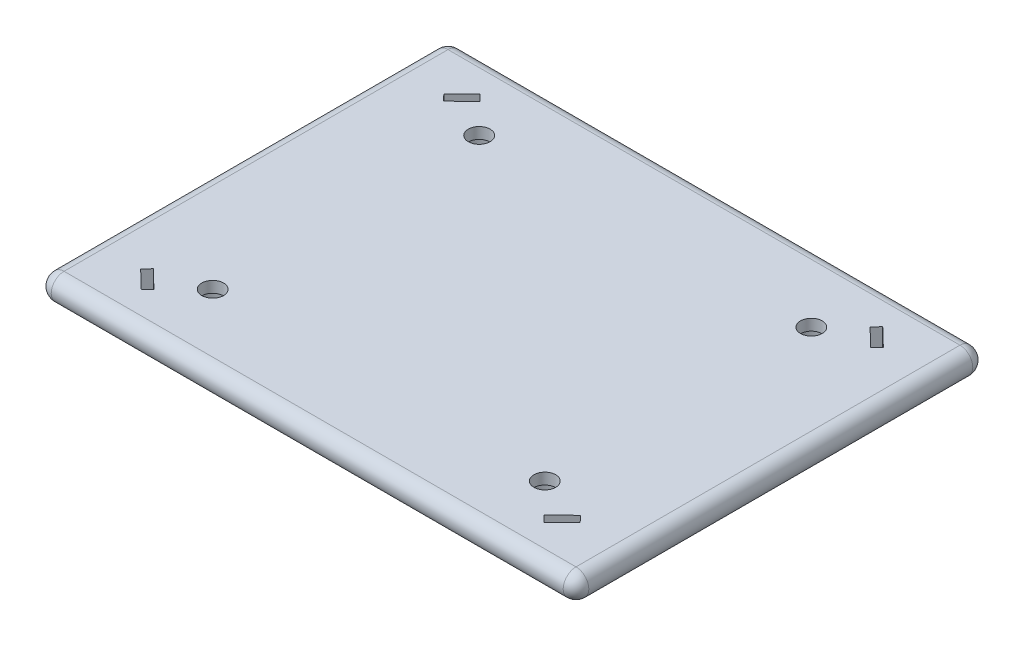
SolidWorks part; units mm, degrees
ref_plane "前视基准面" through (0, 0, 0) normal (0, 0, 1) x (1, 0, 0)
ref_plane "上视基准面" through (0, 0, 0) normal (0, 1, 0) x (1, 0, 0)
ref_plane "右视基准面" through (0, 0, 0) normal (1, 0, 0) x (0, 0, -1)
other "碳"
sketch "草图2" plane through (0, 0, 0) normal (0, 1, 0) x (1, 0, 0)
  line L0 (0, 0) -> (-72.7924, 0) construction
  line L5 (0, 151.7592) -> (0, 201.8849) construction
  line L6 (-200, 160) -> (200, 160)
  line L7 (210, 150) -> (210, 0)
  line L8 (210, 0) -> (210, -150)
  line L9 (200, -160) -> (-200, -160)
  line L10 (-210, 0) -> (-210, -150)
  line L11 (-210, 150) -> (-210, 0)
  line L12 (-157.3287, 132.3214) -> (-171.7157, 118.4284)
  line L13 (-157.3287, 132.3214) -> (-152.4662, 127.2859)
  line L14 (-171.7157, 118.4284) -> (-166.8532, 113.393)
  line L15 (-152.4662, 127.2859) -> (-166.8532, 113.393)
  line L16 (-171.7157, -118.4284) -> (-166.8532, -113.393)
  line L17 (-152.4662, -127.2859) -> (-166.8532, -113.393)
  line L18 (-157.3287, -132.3214) -> (-152.4662, -127.2859)
  line L19 (-157.3287, -132.3214) -> (-171.7157, -118.4284)
  line L20 (157.3287, -132.3214) -> (171.7157, -118.4284)
  line L21 (157.3287, -132.3214) -> (152.4662, -127.2859)
  line L22 (152.4662, -127.2859) -> (166.8532, -113.393)
  line L23 (171.7157, -118.4284) -> (166.8532, -113.393)
  line L24 (171.7157, 118.4284) -> (166.8532, 113.393)
  line L25 (152.4662, 127.2859) -> (166.8532, 113.393)
  line L26 (157.3287, 132.3214) -> (152.4662, 127.2859)
  line L27 (157.3287, 132.3214) -> (171.7157, 118.4284)
  arc A0 (210, -150) -> (200, -160) centre (200, -150) cw
  arc A1 (-210, -150) -> (-200, -160) centre (-200, -150) ccw
  arc A2 (200, 160) -> (210, 150) centre (200, 150) cw
  arc A3 (-210, 150) -> (-200, 160) centre (-200, 150) cw
  circle A4 centre (-129.7453, 104.1081) radius 9.7639 construction
  circle A5 centre (-129.7453, -104.1081) radius 9.7639 construction
  circle A6 centre (129.7453, -104.1081) radius 9.7639 construction
  circle A7 centre (129.7453, 104.1081) radius 9.7639 construction
  point P12 (0, 160)
  point P13 (0, -160)
  point P16 (210, -160)
  point P19 (-210, -160)
  point P22 (210, 160)
  point P25 (-210, 160)
  dimension "D1" = 10
  dimension "D2" = 150
  dimension "D3" = 400
  dimension "D4" = 20
  dimension "D5" = 7
extrude "凸台-拉伸1" add sketch "草图2" along normal blind 20
hole_wizard "5/8 六角头螺钉的柱形沉头孔1" positions "草图15" profile "草图16" counterbore size "5/8" standard "ANSI Inch" end condition through all
sketch "草图15" plane through (0, 0, 0) normal (0, -1, 0) x (-1, 0, 0)
  point P0 (129.7453, -104.1081)
  point P3 (-129.7453, -104.1081)
  point P6 (129.7453, 104.1081)
  point P9 (-129.7453, 104.1081)
  point P17 (129.7453, -104.1081)
sketch "草图16" plane through (-129.7453, 0, 104.1081) normal (1, 0, 0) x (0, 0, -1)
  line L0 (0, 0) -> (0, 20)
  line L1 (0, 20) -> (8.5331, 20)
  line L3 (8.5331, 20) -> (8.5331, 11.2776)
  line L4 (17.4625, 11.2776) -> (8.5331, 11.2776)
  line L5 (17.4625, 11.2776) -> (17.4625, 0.5328)
  line L6 (17.4625, 0.5328) -> (18.0975, 0)
  line L7 (18.0975, 0) -> (0, 0)
  line L8 (-17.4625, 0.5328) -> (-18.0975, 0) construction
  line L11 (0, -6.35) -> (0, 107.95) construction
  dimension "通孔孔直径" = 17.0663
  dimension "通孔孔深度" = 20
  dimension "柱形沉头孔直径" = 34.925
  dimension "柱形沉头孔深度" = 11.2776
  dimension "近端锥形沉头孔直径" = 36.195
  dimension "近端锥形沉头孔角度" = 100
fillet "圆角1" 16 edges at (210, 20, 0) (207.0711, 20, -157.0711) (0, 20, -160) (-207.0711, 20, -157.0711) (-210, 20, 0) (-207.0711, 20, 157.0711) (0, 20, 160) (207.0711, 20, 157.0711) (210, 0, 0) (207.0711, 0, 157.0711) (0, 0, 160) (-207.0711, 0, 157.0711) (-210, 0, 0) (-207.0711, 0, -157.0711) (0, 0, -160) (207.0711, 0, -157.0711) type full round first side face at (129.7453, 20, 95.575) second side face at (129.7453, 0, 86.0106) middle face at (206.0355, 10, 156.0355) middle face at (0, 10, 160) middle face at (-206.0355, 10, 156.0355) middle face at (-210, 10, 0) middle face at (-206.0355, 10, -156.0355) middle face at (210, 10, 0) middle face at (206.0355, 10, -156.0355) middle face at (0, 10, -160)
